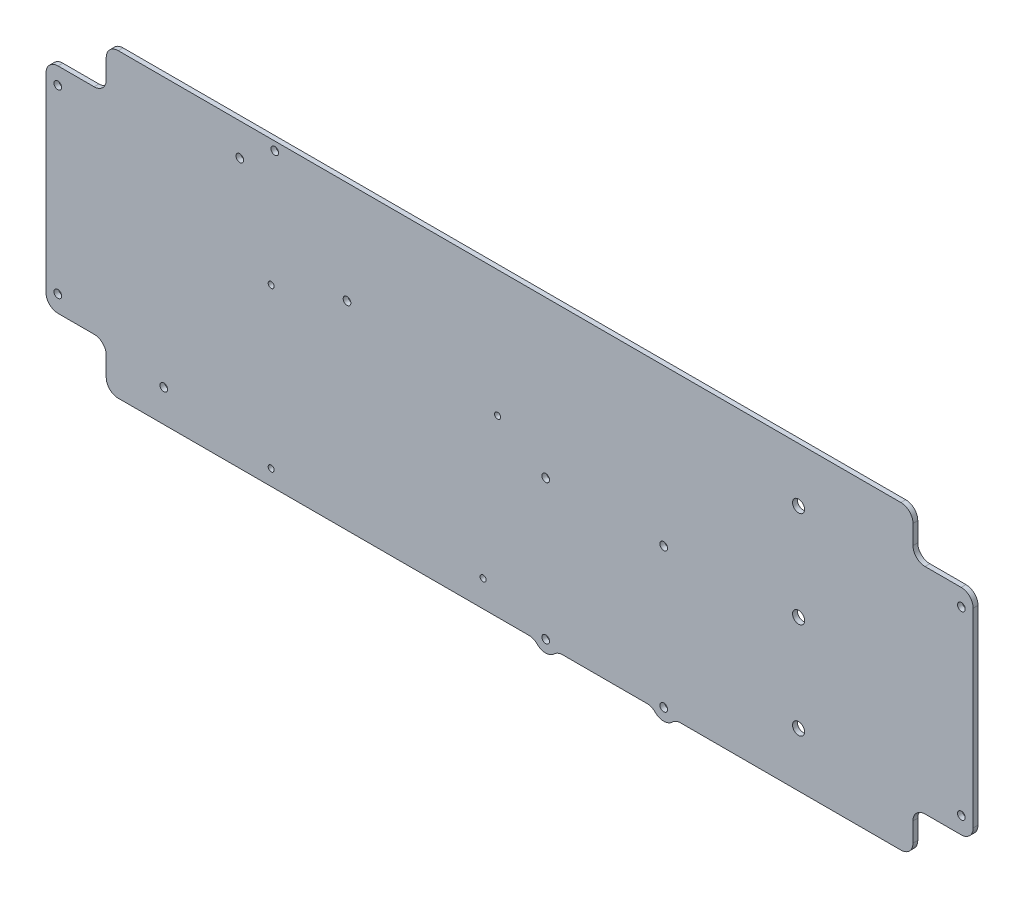
SolidWorks part; units mm, degrees
material "2014 Alloy"
ref_plane "Plan de face" through (0, 0, 0) normal (0, 0, 1) x (1, 0, 0)
ref_plane "Plan de dessus" through (0, 0, 0) normal (0, 1, 0) x (1, 0, 0)
ref_plane "Plan de droite" through (0, 0, 0) normal (1, 0, 0) x (0, 0, -1)
sketch "Sketch1" plane through (0, 0, 0) normal (0, 0, 1) x (1, 0, 0)
  line L1 (-192.5, 62.5) -> (192.5, 62.5)
  line L2 (-192.5, 62.5) -> (-192.5, -62.5)
  line L3 (-192.5, -62.5) -> (192.5, -62.5)
  line L4 (192.5, 62.5) -> (192.5, -62.5)
  line L5 (-192.5, 62.5) -> (192.5, -62.5) construction
  line L6 (-192.5, -62.5) -> (192.5, 62.5) construction
  point P0 (0, 0)
  dimension "D1" = 125
  dimension "D2" = 385
extrude "Boss-Extrude1" add sketch "Sketch1" along normal blind 2
sketch "Sketch2" plane through (0, 0, 2) normal (0, 0, 1) x (1, 0, 0)
  line L1 (-187.6, 37.5) -> (187.6, 37.5) construction
  line L2 (-187.6, 37.5) -> (-187.6, -37.5) construction
  line L3 (-187.6, -37.5) -> (187.6, -37.5) construction
  line L4 (187.6, 37.5) -> (187.6, -37.5) construction
  line L5 (-187.6, 37.5) -> (187.6, -37.5) construction
  line L6 (-187.6, -37.5) -> (187.6, 37.5) construction
  circle A0 centre (-187.6, 37.5) radius 1.6
  circle A1 centre (-187.6, -37.5) radius 1.6
  circle A2 centre (187.6, 37.5) radius 1.6
  circle A3 centre (187.6, -37.5) radius 1.6
  point P0 (0, 0)
  dimension "D1" = 75
  dimension "D2" = 375.2
extrude "Fixing_holes" cut sketch "Sketch2" against normal through all
sketch "Sketch3" plane through (0, 0, 2) normal (0, 0, 1) x (1, 0, 0)
  line L1 (-192.5, 62.5) -> (-167.5, 62.5)
  line L2 (-192.5, 62.5) -> (-192.5, 44.5)
  line L3 (-192.5, 44.5) -> (-167.5, 44.5)
  line L4 (-167.5, 62.5) -> (-167.5, 44.5)
  dimension "D1" = 18
  dimension "D2" = 25
extrude "Cut-Extrude2" cut sketch "Sketch3" against normal through all
mirror "Mirror1" about plane through (0, 0, 0) normal (0, 1, 0) of "Cut-Extrude2"
mirror "Mirror2" about plane through (0, 0, 0) normal (1, 0, 0) of "Mirror1"
sketch "Sketch4" plane through (0, 0, 2) normal (0, 0, 1) x (1, 0, 0)
  line L0 (-99, 10) -> (-5, 10) construction
  line L1 (-99, 10) -> (-99, -56) construction
  circle A0 centre (-99, 10) radius 1.25
  circle A1 centre (-99, -56) radius 1.25
  circle A2 centre (-5, 10) radius 1.25
  circle A3 centre (-11, -51.5) radius 1.25
  dimension "D4" = 66
  dimension "D5" = 94
  dimension "D7" = 61.5
  dimension "D8" = 6
  dimension "D1" = 5
  dimension "D2" = 10
extrude "Cave_board_holes" cut sketch "Sketch4" against normal through all
sketch "Sketch5" plane through (0, 0, 2) normal (0, 0, 1) x (1, 0, 0)
  line L1 (15, -2.4) -> (64, -2.4) construction
  line L2 (15, -2.4) -> (15, -60.4) construction
  line L3 (15, -60.4) -> (64, -60.4) construction
  line L4 (64, -2.4) -> (64, -60.4) construction
  circle A0 centre (15, -2.4) radius 1.6
  circle A1 centre (15, -60.4) radius 1.6
  circle A2 centre (64, -2.4) radius 1.6
  circle A3 centre (64, -60.4) radius 1.6
  dimension "D1" = 58
  dimension "D2" = 49
  dimension "D3" = 15
  dimension "D4" = 2.4
extrude "RPi_holes" cut sketch "Sketch5" against normal through all
sketch "Sketch6" plane through (0, 0, 2) normal (0, 0, 1) x (1, 0, 0)
  line L1 (-97.5, 59) -> (-67.5, 59) construction
  line L2 (-97.5, 59) -> (-97.5, 20) construction
  line L3 (-97.5, 20) -> (-67.5, 20) construction
  line L4 (-67.5, 59) -> (-67.5, 20) construction
  circle A0 centre (-97.5, 59) radius 1.6
  circle A3 centre (-67.5, 20) radius 1.6
  dimension "D1" = 39
  dimension "D2" = 30
  dimension "D3" = 67.5
  dimension "D4" = 20
extrude "buzzer_holes" cut sketch "Sketch6" against normal through all
sketch "Sketch7" plane through (0, 0, 2) normal (0, 0, 1) x (1, 0, 0)
  line L0 (0, 0) -> (178.5314, 0) construction
  circle A0 centre (120, 0) radius 2.5
  circle A1 centre (120, 40) radius 2.5
  circle A2 centre (120, -40) radius 2.5
  dimension "D4" = 120
  dimension "D5" = 40
hole_wizard "Ø0.15 (0.15) Diameter Hole1" positions "Sketch11" profile "Sketch10" hole size "Ø0.15" standard "ISO"
sketch "Sketch11" plane through (0, 0, 2) normal (0, 0, 1) x (1, 0, 0)
  point P0 (120, 40)
  point P3 (120, 0)
  point P6 (120, -40)
sketch "Sketch10" plane through (120, 40, 2) normal (1, 0, 0) x (0, -1, 0)
  line L0 (0, 0) -> (0, 71.5022)
  line L1 (0, 71.5022) -> (2.5, 70)
  line L2 (2.5, 70) -> (2.5, 0)
  line L5 (2.5, 0) -> (0, 0)
  line L10 (0, 71.5022) -> (-2.5, 70) construction
  line L11 (0, -6.35) -> (0, 107.95) construction
  dimension "Hole Dia." = 5
  dimension "Hole Depth" = 70
  dimension "Drill Angle" = 118
sketch "Sketch8" plane through (0, 0, 2) normal (0, 0, 1) x (1, 0, 0)
  line L0 (-167.5, -62.5) -> (167.5, -62.5) construction
  line L2 (10.4624, -62.5) -> (19.5376, -62.5)
  line L3 (59.4624, -62.5) -> (68.5376, -62.5)
  arc A0 (10.4624, -62.5) -> (19.5376, -62.5) centre (15, -60.4) ccw
  arc A1 (59.4624, -62.5) -> (68.5376, -62.5) centre (64, -60.4) ccw
  dimension "D1" = 10
  dimension "D2" = 10
extrude "Boss-Extrude2" add sketch "Sketch8" against normal up to surface (2 mm away) up to face at (122.5, 40, 0)
fillet "Fillet1" radius 5 16 edges at (68.5376, -62.5, 1) (59.4624, -62.5, 1) (19.5376, -62.5, 1) (10.4624, -62.5, 1) (-192.5, 44.5, 1) (-167.5, 44.5, 1) (-167.5, 62.5, 1) (-167.5, -62.5, 1) (-167.5, -44.5, 1) (-192.5, -44.5, 1) (167.5, -62.5, 1) (167.5, -44.5, 1) (192.5, -44.5, 1) (192.5, 44.5, 1) (167.5, 44.5, 1) (167.5, 62.5, 1)
sketch "Sketch9" plane through (0, 0, 2) normal (0, 0, 1) x (1, 0, 0)
  line L0 (-192.5, 39.5) -> (-192.5, -39.5) construction
  line L1 (-162.5, -62.5) -> (7.958, -62.5) construction
  point P0 (-192.5, -62.5)
sketch "Sketch12" plane through (0, 0, 2) normal (0, 0, 1) x (1, 0, 0)
  circle A0 centre (-112, 49.1) radius 1.6
  circle A1 centre (-143.6, -49.1) radius 1.6
  dimension "D1" = 3.2
  dimension "D4" = 3.2
  dimension "D2" = 112
  dimension "D3" = 49.1
  dimension "D5" = 143.6
  dimension "D6" = 49.1
extrude "AC-DC_holes" cut sketch "Sketch12" against normal up to next
